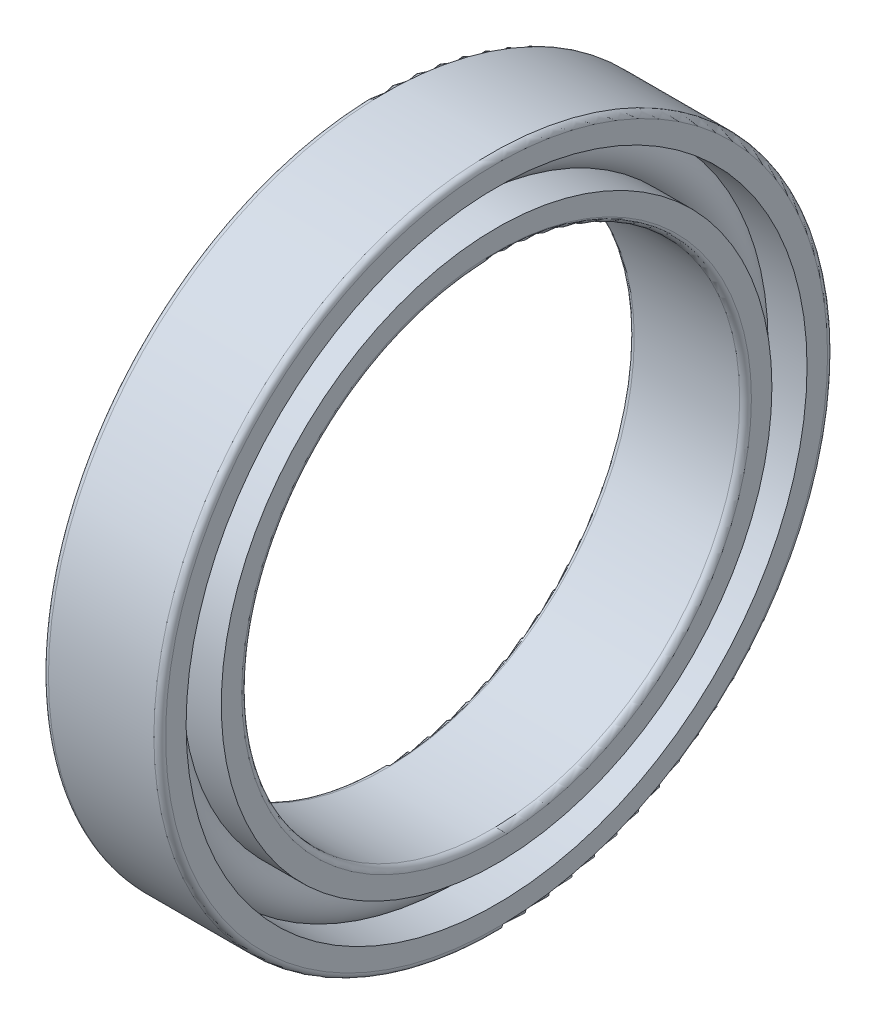
SolidWorks part; units mm, degrees
ref_plane "Plane1" through (0, 0, 0) normal (0, 0, 1) x (1, 0, 0)
ref_plane "Plane2" through (0, 0, 0) normal (0, 1, 0) x (1, 0, 0)
ref_plane "Plane3" through (0, 0, 0) normal (1, 0, 0) x (0, 0, -1)
other "Configuration Table"
sketch "Clipboard" plane through (0, 0, 0) normal (0, 0, 1) x (1, 0, 0)
  line L0 (-10, 0) -> (10, 0) construction
  line L1 (0, 0) -> (22.3471, -0.7804)
  line L2 (0, 0) -> (9.9939, 0.349)
  line L3 (0, 0) -> (22.3471, -0.7804)
  line L4 (0, 0) -> (-22.3573, -0.3902)
  dimension "BallCLRad" = 10
sketch "CagSpiSke" plane through (0, 0, 0) normal (0, 0, 1) x (1, 0, 0)
  line L0 (0.09, 9.85) -> (0.09, 10.15)
  line L1 (0.09, 10.15) -> (-0.09, 10.15)
  line L2 (-0.09, 10.15) -> (-0.09, 9.85)
  line L3 (-0.09, 9.85) -> (0.09, 9.85)
  line L4 (-20.6375, 0) -> (20.6375, 0) construction
  line L5 (0, 0) -> (0, 23.7692) construction
  dimension "OD" = 20.3
  dimension "ID" = 19.7
revolve "CageSpine" add sketch "CagSpiSke" angle 0.001 about L4 reverse direction yes
ref_axis "Axis1" through (-50, 0, 0) along (1, 0, 0)
sketch "CagBalSke" plane through (0, 0, 0) normal (0, 0, 1) x (1, 0, 0)
  line L0 (-0.99, 10) -> (0.99, 10)
  line L1 (-1.905, 10) -> (1.905, 10) construction
  line L2 (-10, 0) -> (10, 0) construction
  line L3 (0, 0) -> (0, 24) construction
  arc A0 (0.99, 10) -> (-0.99, 10) centre (0, 10) cw
  dimension "BallCLRad" = 10
revolve "CageBall" [suppressed] add sketch "CagBalSke" angle 360 about L1 reverse direction yes
pattern_circular "CageBalls" [suppressed] count 2 every 180 about axis through (-50, 0, 0) along (1, 0, 0)
sketch "CagTrmODSke" plane through (0, 0, 0) normal (0, 0, 1) x (1, 0, 0)
  line L0 (0.991, 10.15) -> (0.991, 10.991)
  line L1 (0.991, 10.991) -> (-0.991, 10.991)
  line L2 (-0.991, 10.991) -> (-0.991, 10.15)
  line L3 (-0.991, 10.15) -> (0.991, 10.15)
  line L4 (-20.6375, 0) -> (20.6375, 0) construction
  line L5 (0, 0) -> (0, 25) construction
  dimension "Width" = 1.982
  dimension "ID" = 20.3
  dimension "OD" = 21.982
revolve "CageTrimOD" [suppressed] cut sketch "CagTrmODSke" angle 360 about L4 reverse direction yes
sketch "CagTrmIDSke" plane through (0, 0, 0) normal (0, 0, 1) x (1, 0, 0)
  line L0 (0.991, 9.011) -> (0.991, 9.85)
  line L1 (0.991, 9.85) -> (-0.991, 9.85)
  line L2 (-0.991, 9.85) -> (-0.991, 9.011)
  line L3 (-0.991, 9.011) -> (0.991, 9.011)
  line L4 (-20.6375, 0) -> (20.6375, 0) construction
  line L5 (0, 0) -> (0, 25) construction
  dimension "Width" = 1.982
  dimension "ID" = 18.022
  dimension "OD" = 19.7
revolve "CageTrimID" [suppressed] cut sketch "CagTrmIDSke" angle 360 about L4 reverse direction yes
sketch "BalSimSke" plane through (0, 0, 0) normal (0, 0, 1) x (1, 0, 0)
  line L0 (-10, 0) -> (10, 0) construction
  line L1 (-10, 10) -> (10, 10) construction
  line L2 (0, 0) -> (0, 23) construction
  circle A0 centre (0, 10) radius 0.9
  dimension "BallCLRad" = 10
  dimension "Ball_diameter" = 1.8
revolve "BallsSimplified" add sketch "BalSimSke" angle 360 about L0
sketch "BalDetSke" plane through (0, 0, 0) normal (0, 0, 1) x (1, 0, 0)
  line L0 (-0.9, 10) -> (0.9, 10)
  line L1 (-1.905, 10) -> (1.905, 10) construction
  line L2 (0, 0) -> (0, 25) construction
  arc A0 (0.9, 10) -> (-0.9, 10) centre (0, 10) cw
  dimension "BallCLRad" = 10
  dimension "Ball_diameter" = 1.8
revolve "BallDetailed" [suppressed] add sketch "BalDetSke" angle 360 about L1 reverse direction yes
sketch "InnRacSke" plane through (0, 0, 0) normal (0, 0, 1) x (1, 0, 0)
  line L0 (-0.6369, 9.4) -> (-2, 9.4)
  line L1 (-2, 9.4) -> (-2, 8.7)
  line L2 (-1.8, 8.5) -> (1.8, 8.5)
  line L3 (2, 8.7) -> (2, 9.4)
  line L4 (2, 9.4) -> (0.6369, 9.4)
  line L5 (-20.6375, 0) -> (20.6375, 0) construction
  line L6 (0, 0) -> (0, 30) construction
  arc A0 (-2, 8.7) -> (-1.8, 8.5) centre (-1.8, 8.7) ccw
  arc A1 (1.8, 8.5) -> (2, 8.7) centre (1.8, 8.7) ccw
  arc A2 (0.6369, 9.4) -> (-0.6369, 9.4) centre (0, 10) cw
  dimension "BallCLRad" = 10
  dimension "Fillet_radius" = 0.2
  dimension "Ball_diameter" = 1.75
  dimension "ID" = 17
  dimension "OD" = 18.8
  dimension "Width" = 4
revolve "InnerRace" add sketch "InnRacSke" angle 360 about L5 reverse direction yes
sketch "OutRacSke" plane through (0, 0, 0) normal (0, 0, 1) x (1, 0, 0)
  line L0 (-0.6369, 10.6) -> (-2, 10.6)
  line L1 (-2, 10.6) -> (-2, 11.3)
  line L2 (-1.8, 11.5) -> (1.8, 11.5)
  line L3 (2, 11.3) -> (2, 10.6)
  line L4 (2, 10.6) -> (0.6369, 10.6)
  line L5 (-20.6375, 0) -> (20.6375, 0) construction
  line L6 (0, 0) -> (0, 30) construction
  arc A0 (-2, 11.3) -> (-1.8, 11.5) centre (-1.8, 11.3) cw
  arc A1 (1.8, 11.5) -> (2, 11.3) centre (1.8, 11.3) cw
  arc A2 (0.6369, 10.6) -> (-0.6369, 10.6) centre (0, 10) ccw
  dimension "BallCLRad" = 10
  dimension "Fillet_radius" = 0.2
  dimension "Ball_diameter" = 1.75
  dimension "Width" = 4
revolve "OuterRace" add sketch "OutRacSke" angle 360 about L5 reverse direction yes
pattern_circular "BallsDetailed" [suppressed] count 2 over 360 about axis through (-50, 0, 0) along (1, 0, 0) reverse direction yes
equation "\"BallCLRad@Clipboard\" = ( \"OD@OutRacSke\" + \"ID@InnRacSke\" ) / 4"
equation "\"BallCLRad@BalSimSke\" = \"BallCLRad@Clipboard\""
equation "\"BallCLRad@BalDetSke\" = \"BallCLRad@Clipboard\""
equation "\"BallCLRad@InnRacSke\" = \"BallCLRad@Clipboard\""
equation "\"BallCLRad@OutRacSke\" = \"BallCLRad@Clipboard\""
equation "\"Ball_diameter@InnRacSke\" = \"Ball_diameter@BalDetSke\" - 0.05"
equation "\"Ball_diameter@OutRacSke\" = \"Ball_diameter@BalDetSke\" - 0.05"
equation "\"Ball_diameter@BalSimSke\" = \"Ball_diameter@BalDetSke\""
equation "\"Fillet_radius@OutRacSke\" = \"Fillet_radius@InnRacSke\""
equation "\"Max_count@Clipboard\" = int( 3.14159265 / atn(( \"Ball_diameter@BalDetSke\" / 2) / sqr( \"BallCLRad@Clipboard\"  *  \"BallCLRad@Clipboard\" - ( \"Ball_diameter@BalDetSke\" / 2) *  ( \"Ball_diameter@BalDetSke\" / 2))))"
equation "\"Max_count@Clipboard\" = ((sgn( \"Max_count@Clipboard\" - \"Count@Clipboard\" )-1)*( \"Max_count@Clipboard\" - \"Count@Clipboard\" ))/-2+ \"Count@Clipboard\""
equation "\"Count@BallsDetailed\" = int( \"Show_count@Clipboard\" ) "
equation "\"Count@BallsDetailed\" = ((sgn( \"Count@BallsDetailed\" - \"Max_count@Clipboard\" )-1)*( \"Count@BallsDetailed\" - \"Max_count@Clipboard\" ))/-2+ \"Max_count@Clipboard\""
equation "\"Count@BallsDetailed\" = ((sgn( \"Count@BallsDetailed\" - \"Min_count@Clipboard\" )+1)*( \"Count@BallsDetailed\" - \"Min_count@Clipboard\"))/2 +\"Min_count@Clipboard\""
equation "\"Angle@BallsDetailed\" = 360.0 / \"Max_count@Clipboard\""
equation "\"BallCLRad@CagBalSke\" = \"BallCLRad@Clipboard\""
equation "\"Count@CageBalls\" = \"Count@BallsDetailed\""
equation "\"Angle@CageBalls\" = \"Angle@BallsDetailed\""
equation "\"Angle@CageSpine\" =  \"Angle@CageBalls\" * ( \"Count@CageBalls\" -1 + int( \"Count@CageBalls\" / \"Max_count@Clipboard\" ) )  + 0.001 -  int( \"Count@CageBalls\" / \"Max_count@Clipboard\" ) * 0.001"
equation "\"Angle@CageSpine\" =  \"Angle@CageSpine\" * int( \"Min_count@Clipboard\" / 2) + int(1 / \"Min_count@Clipboard\")  * 0.001"
equation "\"CageWallOD@CagBalSke\" =  \"Ball_diameter@BalDetSke\" * 1.1"
equation "\"Thickness@CagSpiSke\" =  \"Ball_diameter@BalDetSke\" * 0.1"
equation "\"OD@CagTrmODSke\" = \"BallCLRad@Clipboard\" * 2 + \"CageWallOD@CagBalSke\" + 0.002"
equation "\"ID@CagTrmODSke\" = \"BallCLRad@Clipboard\" * 2 + \"Ball_diameter@BalDetSke\" / 6"
equation "\"OD@CagTrmIDSke\" = \"BallCLRad@Clipboard\" * 2 - \"Ball_diameter@BalDetSke\" / 6"
equation "\"ID@CagTrmIDSke\" = \"BallCLRad@Clipboard\" * 2 - \"CageWallOD@CagBalSke\" + 0.002"
equation "\"OD@CagSpiSke\" = \"ID@CagTrmODSke\""
equation "\"ID@CagSpiSke\" = \"OD@CagTrmIDSke\""
equation "\"Width@CagTrmODSke\" = \"CageWallOD@CagBalSke\" + 0.002"
equation "\"Width@CagTrmIDSke\" = \"CageWallOD@CagBalSke\" + 0.002"
